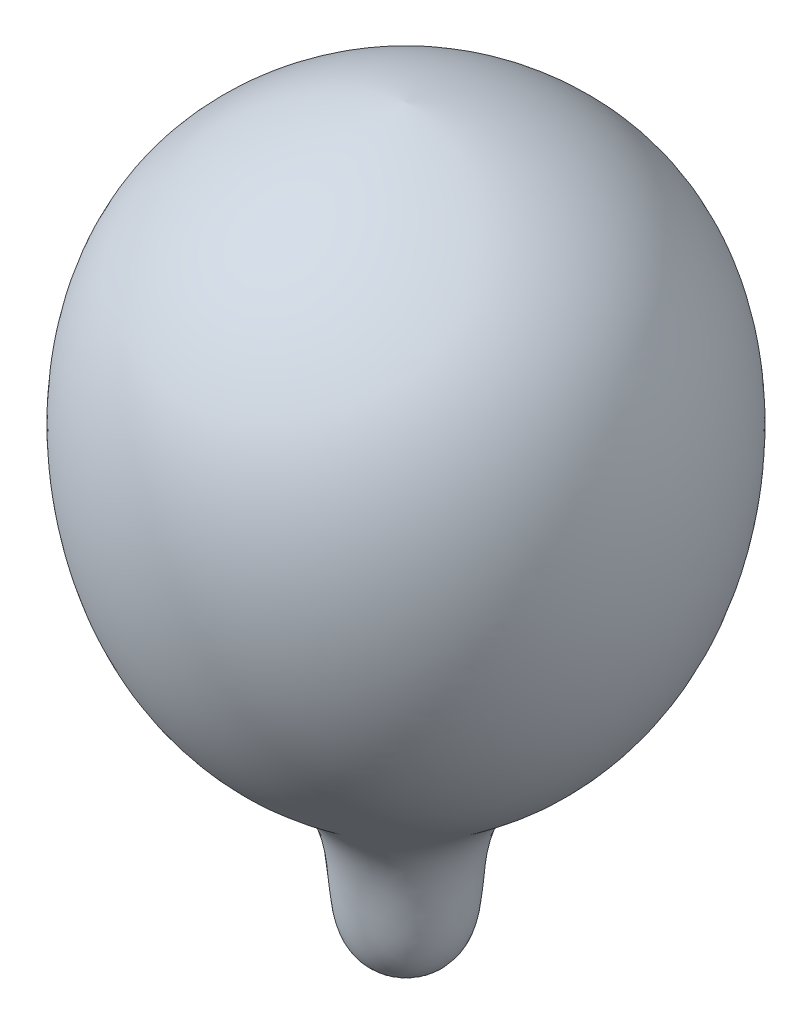
SolidWorks part; units mm, degrees
ref_plane "Front Plane"
ref_plane "Top Plane" through (0, 0, 0) normal (0, 1, 0) x (1, 0, 0)
ref_plane "Right Plane" through (0, 0, 0) normal (1, 0, 0) x (0, 0, -1)
sketch "Sketch1" plane through (0, 0, 0) normal (0, 0, 1) x (1, 0, 0)
  line L0 (170.1215, 307.7155) -> (170.1215, -418.5802)
  line L1 (0, 154.3767) -> (0, -347.2947) construction
  line L2 (-170.1215, 307.7155) -> (-170.1215, -418.5802)
  line L3 (0, -347.2947) -> (0, -406.0532)
  spline S0 degree 3 poles (0, 154.3767) (50.7896, 148.7459) (163.9011, 96.3448) (181.829, -79.7738) (121.3347, -195.7702) (45.7716, -239.5698) (33.8172, -300.6883) (37.7025, -340.3462) (0, -347.2947) knots 0 0 0 0 0.244026 0.505633 0.717447 0.831784 0.876368 1 1 1 1
  spline S1 degree 3 poles (0, 154.3767) (-50.7896, 148.7459) (-163.9011, 96.3448) (-181.829, -79.7738) (-121.3347, -195.7702) (-45.7716, -239.5698) (-33.8172, -300.6883) (-37.7025, -340.3462) (0, -347.2947) knots 0 0 0 0 0.244026 0.505633 0.717447 0.831784 0.876368 1 1 1 1
  point P21 (0.761, -348.1066)
  point P23 (0, -372.6947)
  point P24 (-0.0104, -347.3128)
  point P25 (-5.7429, -351.5406)
  point P26 (0.0082, -355.7682)
  point P27 (170.2831, -418.8373)
  point P28 (0, -406.0532)
  point P29 (170.1215, -418.5802)
  point P30 (0, -347.2947)
  dimension "D1" = 340.243
  dimension "D2" = 25.4
revolve "Revolve1" add sketch "Sketch1" angle 360 about L1 region at (68.8245, -59.9805, 0)
